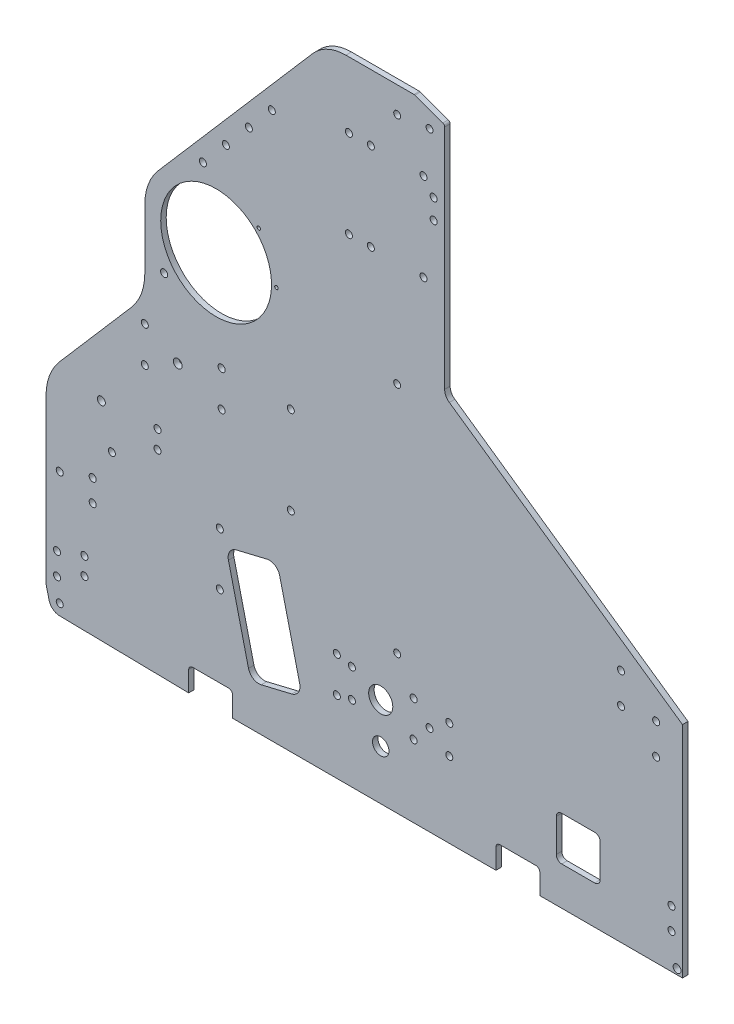
SolidWorks part; units mm, degrees
ref_plane "Front Plane" through (0, 0, 0) normal (0, 0, 1) x (1, 0, 0)
ref_plane "Top Plane" through (0, 0, 0) normal (0, 1, 0) x (1, 0, 0)
ref_plane "Right Plane" through (0, 0, 0) normal (1, 0, 0) x (0, 0, -1)
sketch "Sketch1" plane through (0, 0, 0) normal (0, 0, 1) x (1, 0, 0)
  line L0 (82.55, -20.32) -> (82.55, -6.35)
  line L2 (0, 0) -> (0, 157.48)
  line L4 (368.3, -20.32) -> (368.3, 106.68)
  line L5 (82.55, -6.35) -> (107.95, -6.35)
  line L6 (107.95, -6.35) -> (107.95, -20.32)
  line L7 (107.95, -20.32) -> (260.35, -20.32)
  line L8 (260.35, -20.32) -> (260.35, -6.35)
  line L9 (260.35, -6.35) -> (285.75, -6.35)
  line L10 (285.75, -6.35) -> (285.75, -20.32)
  line L11 (285.75, -20.32) -> (368.3, -20.32)
  line L12 (361.95, 12.7) -> (368.3, 12.7) construction
  line L13 (0, 0) -> (6.35, 0) construction
  line L14 (0.1896, -7.8901) -> (1.7771, -14.2401)
  line L15 (7.8295, -19.0491) -> (82.55, -20.32)
  line L16 (0, 0) -> (0, -6.35)
  line L17 (76.2, 141.605) -> (79.375, 141.605) construction
  line L18 (57.15, 131.2863) -> (101.6, 131.2862) construction
  line L19 (57.15, 131.2863) -> (57.15, 151.9238) construction
  line L20 (101.6, 131.2862) -> (101.6, 151.9237) construction
  line L21 (57.15, 151.9238) -> (101.6, 151.9237) construction
  line L22 (57.15, 131.2863) -> (101.6, 151.9237) construction
  line L23 (101.6, 131.2862) -> (57.15, 151.9238) construction
  line L25 (203.2, 59.805) -> (203.2, 194.805) construction
  line L26 (203.2, 194.805) -> (203.2, 329.805) construction
  line L27 (355.6, 332.105) -> (330.2, 332.105) construction
  line L28 (330.2, 332.105) -> (330.2, 217.805) construction
  line L29 (330.2, 217.805) -> (355.6, 217.805) construction
  line L30 (355.6, 217.805) -> (355.6, 332.105) construction
  line L31 (203.2, 344.805) -> (203.2, 194.805) construction
  line L32 (50.8, 332.105) -> (76.2, 332.105) construction
  line L33 (76.2, 332.105) -> (76.2, 217.805) construction
  line L34 (50.8, 217.805) -> (50.8, 332.105) construction
  line L35 (76.2, 217.805) -> (50.8, 217.805) construction
  line L36 (213.2, 344.805) -> (230.6638, 338.455)
  line L37 (203.2, 344.805) -> (161.925, 344.805)
  line L38 (203.2, 344.805) -> (213.2, 344.805)
  line L39 (348.5362, 344.805) -> (413.4623, 344.805)
  line L40 (348.5362, 344.805) -> (230.6638, 344.805) construction
  line L42 (161.925, 344.805) -> (0, 157.48)
  line L44 (230.6638, 338.455) -> (230.6638, 202.565)
  line L45 (230.6638, 202.565) -> (368.3, 106.68)
  line L46 (213.2, 344.805) -> (-141.0713, 344.805) construction
  circle A0 centre (6.35, 0) radius 2.032
  circle A1 centre (6.35, 12.7) radius 2.032
  circle A2 centre (361.95, 0) radius 2.032
  circle A3 centre (361.95, 12.7) radius 2.032
  arc A5 (1.7771, -14.2401) -> (7.8295, -19.0491) centre (7.9375, -12.7) ccw
  circle A6 centre (7.9375, -12.7) radius 2.032
  arc A7 (0, -6.35) -> (0.1896, -7.8901) centre (6.35, -6.35) ccw
  circle A8 centre (38.1, 78.105) radius 2.032
  circle A9 centre (76.2, 141.605) radius 2.54
  circle A10 centre (101.6, 131.2862) radius 2.032
  circle A11 centre (101.6, 151.9237) radius 2.032
  circle A12 centre (57.15, 151.9238) radius 2.032
  circle A13 centre (57.15, 131.2863) radius 2.032
  circle A15 centre (203.2, 59.805) radius 2
  circle A16 centre (203.2, 194.805) radius 2
  circle A17 centre (203.2, 329.805) radius 2
  circle A18 centre (63.5, 313.055) radius 2.032
  circle A20 centre (355.6, 332.105) radius 2.032
  circle A21 centre (330.2, 332.105) radius 2.032
  circle A22 centre (355.6, 217.805) radius 2.032
  circle A23 centre (330.2, 217.805) radius 2.032
  circle A24 centre (50.8, 332.105) radius 2.032
  circle A25 centre (76.2, 332.105) radius 2.032
  circle A26 centre (50.8, 217.805) radius 2.032
  circle A27 centre (76.2, 217.805) radius 2.032
  circle A28 centre (221.9319, 332.105) radius 2
  circle A29 centre (224.3138, 298.831) radius 2.032
  circle A30 centre (353.06, 100.7351) radius 2.032
  circle A31 centre (332.74, 115.9751) radius 2.032
  circle A32 centre (332.74, 98.1951) radius 2.032
  circle A33 centre (353.06, 82.9551) radius 2.032
  circle A34 centre (117.3562, 280.4276) radius 2.032
  circle A35 centre (104.0678, 265.0548) radius 2.032
  circle A36 centre (90.7795, 249.682) radius 2.032
  circle A38 centre (130.6445, 295.8004) radius 2.032
  circle A39 centre (68.326, 182.9237) radius 2.032
  circle A40 centre (224.3138, 287.401) radius 2.032
  point P82 (203.2, 344.805)
  point P83 (221.9319, 341.63)
  point P90 (368.3, 62.484)
  dimension "D6" = 4.064
  dimension "D10" = 6.35
  dimension "D11" = 4.064
  dimension "D17" = 38.1
  dimension "D27" = 4
  dimension "D31" = 4.064
  dimension "D32" = 41.275
  dimension "D36" = 4.064
  dimension "D47" = 39.624
  dimension "D48" = 4.064
  dimension "D25" = 5.08
  dimension "D26" = 4.064
  dimension "D52" = 4.064
  dimension "D65" = 4.064
  dimension "D2" = 127
  dimension "D3" = 13.97
  dimension "D4" = 25.4
  dimension "D5" = 152.4
  dimension "D7" = 12.7
  dimension "D8" = 6.35
  dimension "D9" = 20.32
  dimension "D12" = 12.7
  dimension "D13" = 1.5875
  dimension "D14" = 82.55
  dimension "D15" = 368.3
  dimension "D16" = 6.35
  dimension "D18" = 98.425
  dimension "D19" = 38.1
  dimension "D20" = 63.5
  dimension "D21" = 3.175
  dimension "D22" = 270
  dimension "D23" = 20.6375
  dimension "D24" = 44.45
  dimension "D28" = 135
  dimension "D29" = 12.7
  dimension "D30" = 15
  dimension "D33" = 63.5
  dimension "D34" = 27.4638
  dimension "D35" = 12.7
  dimension "D37" = 114.3
  dimension "D38" = 25.4
  dimension "D39" = 12.7
  dimension "D40" = 157.48
  dimension "D41" = 142.24
  dimension "D42" = 365.125
  dimension "D43" = 10
  dimension "D44" = 6.35
  dimension "D45" = 31.75
  dimension "D46" = 6.35
  dimension "D49" = 6.35
  dimension "D50" = 203.2
  dimension "D51" = 15.24
  dimension "D53" = 17.78
  dimension "D54" = 17.78
  dimension "D55" = 20.32
  dimension "D56" = 15.24
  dimension "D57" = 92.202
  dimension "D58" = 8.382
  dimension "D59" = 20.32
  dimension "D60" = 20.32
  dimension "D61" = 8.382
  dimension "D62" = 20.32
  dimension "D63" = 8.382
  dimension "D64" = 8.382
  dimension "D66" = 35.052
  dimension "D67" = 68.326
  dimension "D68" = 11.43
extrude "Boss-Extrude1" add sketch "Sketch1" along normal blind 3.175 contours L16 A7 L14 A5 L15 L2 A0 A1 A6 region at (171.3489, 119.5243, 0)
fillet "Fillet1" radius 2.286 4 edges at (285.75, -6.35, 1.5875) (107.95, -6.35, 1.5875) (260.35, -6.35, 1.5875) (82.55, -6.35, 1.5875)
fillet "Fillet2" radius 6.35 1 edges at (230.6638, 202.565, 1.5875)
sketch "Sketch2" plane through (0, 0, 0) normal (0, 0, -1) x (-1, 0, 0)
  circle A0 centre (-100.5528, 71.086) radius 2.032 construction
  circle A1 centre (-100.5528, 40.606) radius 2.032 construction
  circle A2 centre (-22.225, 18.2025) radius 2.032 construction
  circle A3 centre (-22.225, 8.0425) radius 2.032 construction
  circle A4 centre (-100.5528, 71.086) radius 2.032
  circle A5 centre (-100.5528, 40.606) radius 2.032
  circle A6 centre (-22.225, 18.2025) radius 2.032
  circle A7 centre (-22.225, 8.0425) radius 2.032
extrude "Cut-Extrude1" cut sketch "Sketch2" against normal through all
fillet "Fillet3" radius 1.5875 2 edges at (230.6638, 338.455, 1.5875) (213.2, 344.805, 1.5875)
sketch "Sketch3" plane through (0, 0, 3.175) normal (0, 0, 1) x (1, 0, 0)
  line L0 (132.9524, 63.2646) -> (132.7215, 64.2281) construction
  line L1 (128.3814, 66.8897) -> (110.6828, 62.6472) construction
  line L2 (114.5132, 58.4237) -> (126.8822, 61.3887) construction
  line L3 (108.0212, 58.3071) -> (108.2522, 57.3436) construction
  line L4 (131.2006, 57.703) -> (140.0164, 20.9265) construction
  line L5 (144.0993, 16.7636) -> (132.9524, 63.2646) construction
  line L6 (108.2522, 57.3436) -> (119.3991, 10.8426) construction
  line L7 (121.1509, 16.4042) -> (112.3351, 53.1807) construction
  line L8 (119.3991, 10.8426) -> (119.6301, 9.8791) construction
  line L9 (144.3303, 15.8001) -> (144.0993, 16.7636) construction
  line L10 (137.8383, 15.6835) -> (125.4694, 12.7185) construction
  line L11 (123.9701, 7.2175) -> (141.6687, 11.4601) construction
  line L12 (132.9524, 63.2646) -> (132.7215, 64.2281)
  line L13 (128.3814, 66.8897) -> (110.6828, 62.6472)
  line L14 (114.5132, 58.4237) -> (126.8822, 61.3887)
  line L15 (108.0212, 58.3071) -> (108.2522, 57.3436)
  line L16 (131.2006, 57.703) -> (140.0164, 20.9265)
  line L17 (144.0993, 16.7636) -> (132.9524, 63.2646)
  line L18 (108.2522, 57.3436) -> (119.3991, 10.8426)
  line L19 (121.1509, 16.4042) -> (112.3351, 53.1807)
  line L20 (119.3991, 10.8426) -> (119.6301, 9.8791)
  line L21 (144.3303, 15.8001) -> (144.0993, 16.7636)
  line L22 (137.8383, 15.6835) -> (125.4694, 12.7185)
  line L23 (123.9701, 7.2175) -> (141.6687, 11.4601)
  line L24 (127.7894, 69.3598) -> (110.0908, 65.1172)
  line L25 (105.5512, 57.715) -> (105.7822, 56.7515)
  line L26 (105.7822, 56.7515) -> (116.9291, 10.2505)
  line L27 (116.9291, 10.2505) -> (117.16, 9.287)
  line L28 (124.5622, 4.7475) -> (142.2608, 8.99)
  line L29 (146.8003, 16.3922) -> (146.5694, 17.3557)
  line L30 (146.5694, 17.3557) -> (135.4225, 63.8567)
  line L31 (135.4225, 63.8567) -> (135.1915, 64.8202)
  line L32 (14.605, -0.1369) -> (103.7278, 32.3011) construction
  line L33 (14.605, -0.1369) -> (103.7278, 32.3011)
  line L34 (0, -6.35) -> (0, 157.48) construction
  line L35 (-39.6666, 74.7152) -> (103.7278, 126.9065) construction
  line L36 (26.9875, 46.9531) -> (26.9875, 59.6531) construction
  line L37 (107.95, -20.32) -> (260.35, -20.32) construction
  line L38 (64.5259, 92.5258) -> (64.5259, 102.9405) construction
  arc A0 (132.7215, 64.2281) -> (128.6308, 66.9403) centre (129.2206, 63.3889) ccw construction
  arc A1 (110.6828, 62.6472) -> (110.4377, 62.5791) centre (111.522, 59.1463) ccw construction
  arc A2 (128.6308, 66.9403) -> (128.3814, 66.8897) centre (129.2206, 63.3889) ccw construction
  arc A3 (110.4377, 62.5791) -> (108.0212, 58.3071) centre (111.522, 59.1463) ccw construction
  arc A4 (119.6301, 9.8791) -> (123.7207, 7.1669) centre (123.1309, 10.7183) ccw construction
  arc A5 (141.9139, 11.5281) -> (144.3303, 15.8001) centre (140.8295, 14.9609) ccw construction
  arc A6 (141.6687, 11.4601) -> (141.9139, 11.5281) centre (140.8295, 14.9609) ccw construction
  arc A7 (123.7207, 7.1669) -> (123.9701, 7.2175) centre (123.1309, 10.7183) ccw construction
  arc A8 (132.7215, 64.2281) -> (128.6308, 66.9403) centre (129.2206, 63.3889) ccw
  arc A9 (110.6828, 62.6472) -> (110.4377, 62.5791) centre (111.522, 59.1463) ccw
  arc A10 (128.6308, 66.9403) -> (128.3814, 66.8897) centre (129.2206, 63.3889) ccw
  arc A11 (110.4377, 62.5791) -> (108.0212, 58.3071) centre (111.522, 59.1463) ccw
  arc A12 (119.6301, 9.8791) -> (123.7207, 7.1669) centre (123.1309, 10.7183) ccw
  arc A13 (141.9139, 11.5281) -> (144.3303, 15.8001) centre (140.8295, 14.9609) ccw
  arc A14 (141.6687, 11.4601) -> (141.9139, 11.5281) centre (140.8295, 14.9609) ccw
  arc A15 (123.7207, 7.1669) -> (123.9701, 7.2175) centre (123.1309, 10.7183) ccw
  arc A16 (110.0908, 65.1172) -> (109.6726, 65.0012) centre (111.522, 59.1463) ccw
  arc A17 (109.6726, 65.0012) -> (105.5512, 57.715) centre (111.522, 59.1463) ccw
  arc A18 (117.16, 9.287) -> (124.1369, 4.6613) centre (123.1309, 10.7183) ccw
  arc A19 (124.1369, 4.6613) -> (124.5622, 4.7475) centre (123.1309, 10.7183) ccw
  arc A20 (142.2608, 8.99) -> (142.6789, 9.1061) centre (140.8295, 14.9609) ccw
  arc A21 (142.6789, 9.1061) -> (146.8003, 16.3922) centre (140.8295, 14.9609) ccw
  arc A22 (135.1915, 64.8202) -> (128.2147, 69.446) centre (129.2206, 63.3889) ccw
  arc A23 (128.2147, 69.446) -> (127.7894, 69.3598) centre (129.2206, 63.3889) ccw
  circle A26 centre (133.35, 208.2281) radius 1.016 construction
  circle A33 centre (26.9875, 46.9531) radius 2.032
  circle A34 centre (26.9875, 59.6531) radius 2.032
  circle A35 centre (7.9375, 53.3031) radius 2.032
  circle A37 centre (32.0306, 100.8109) radius 31.75 construction
  circle A38 centre (32.0306, 100.8109) radius 2.286
  circle A39 centre (123.1207, 232.9238) radius 1.016 construction
  circle A40 centre (64.5259, 102.9405) radius 2.032
  circle A41 centre (64.5259, 92.5258) radius 2.032
  circle A42 centre (133.35, 208.2281) radius 1.016
  circle A43 centre (123.1207, 232.9238) radius 1.016
  ellipse E0 centre (124.5974, 48.8487) end of major axis (128.5376, 61.3578) minor radius 6 (131.2006, 57.703) -> (126.8822, 61.3887) ccw construction
  ellipse E1 centre (122.2349, 48.2824) end of major axis (113.0518, 57.6456) minor radius 6 (114.5132, 58.4237) -> (112.3351, 53.1807) ccw construction
  ellipse E2 centre (127.7541, 25.2585) end of major axis (131.6942, 37.7675) minor radius 6 (121.1509, 16.4042) -> (125.4694, 12.7185) ccw construction
  ellipse E3 centre (130.1166, 25.8248) end of major axis (139.2998, 16.4616) minor radius 6 (137.8383, 15.6835) -> (140.0164, 20.9265) ccw construction
  ellipse E4 centre (124.5974, 48.8487) end of major axis (120.6573, 36.3397) minor radius 6 (131.2006, 57.703) -> (126.8822, 61.3887) ccw
  ellipse E5 centre (122.2349, 48.2824) end of major axis (131.4181, 38.9192) minor radius 6 (114.5132, 58.4237) -> (112.3351, 53.1807) ccw
  ellipse E6 centre (127.7541, 25.2585) end of major axis (131.6942, 37.7675) minor radius 6 (121.1509, 16.4042) -> (125.4694, 12.7185) ccw
  ellipse E7 centre (130.1166, 25.8248) end of major axis (139.2998, 16.4616) minor radius 6 (137.8383, 15.6835) -> (140.0164, 20.9265) ccw
  point P93 (26.9875, 53.3031)
  point P115 (32.0306, 100.8109)
  dimension "D3" = 63.5
  dimension "D4" = 4.572
  dimension "D8" = 4.064
  dimension "D2" = 88.9
  dimension "D5" = 7.9375
  dimension "D6" = 19.05
  dimension "D7" = 73.6231
  dimension "D9" = 12.7
  dimension "D10" = 10.4147
  dimension "D11" = 37.5384
  dimension "D12" = 45.5727
  dimension "D1" = 2.54
extrude "Cut-Extrude2" cut sketch "Sketch3" against normal through all contours A22 A23 L24 A16 A17 L25 L26 L27 A18 A19 L28 A20 A21 L29 L30 L31 A15 A12 L20 L18 L15 A11 A9 L13 A10 A8 L12 L17 L21 A13 A14 L23 | A12 A15 L23 A14 A13 L21 L17 L12 A8 A10 L13 A9 A11 L15 L18 L20 E7 L22 E6 L19 E5 L14 E4 L16 | L22 E7 L16 E4 L14 E5 L19 E6 | A38 | A41 | A40 | A35 | A34 | A33 | A43 | A42 region at (137.844, 39.8506, 3.175) region at (126.1758, 37.0536, 3.175) region at (128.1544, 68.6507, 3.175) region at (32.0306, 100.8109, 3.175) region at (64.5259, 102.9405, 3.175) region at (64.5259, 92.5258, 3.175)
sketch "Sketch4" plane through (0, 0, 3.175) normal (0, 0, 1) x (1, 0, 0)
  line L0 (57.15, 151.9238) -> (101.6, 151.9237) construction
  line L1 (168.275, 21.4312) -> (212.725, 21.4312) construction
  line L2 (168.275, 21.4312) -> (168.275, 42.0687) construction
  line L3 (168.275, 42.0687) -> (212.725, 42.0687) construction
  line L4 (212.725, 21.4312) -> (212.725, 42.0687) construction
  line L5 (168.275, 21.4312) -> (212.725, 42.0687) construction
  line L6 (168.275, 42.0687) -> (212.725, 21.4312) construction
  line L7 (57.15, 131.2863) -> (57.15, 151.9238) construction
  line L8 (107.95, -20.32) -> (260.35, -20.32) construction
  line L9 (193.675, 31.75) -> (177.005, 31.75) construction
  line L10 (190.5, 31.75) -> (193.675, 31.75) construction
  line L11 (6.35, 12.7) -> (361.95, 12.7) construction
  line L12 (107.95, -6.35) -> (107.95, -20.32) construction
  line L13 (193.675, 31.75) -> (220.6625, 31.75) construction
  line L14 (177.005, 23.4569) -> (177.005, 40.0431) construction
  line L15 (213.2, 44.805) -> (193.2, 44.805) construction
  line L16 (213.2, 44.805) -> (213.2, 344.805) construction
  line L17 (213.2, 344.805) -> (193.2, 344.805) construction
  line L18 (193.2, 44.805) -> (193.2, 344.805) construction
  line L19 (213.2, 44.805) -> (193.2, 344.805) construction
  line L20 (213.2, 344.805) -> (193.2, 44.805) construction
  line L21 (226.9319, 332.105) -> (226.9319, 31.75) construction
  line L22 (237.33, 40.0431) -> (233.3612, 40.0431) construction
  line L23 (237.33, 23.4569) -> (233.3612, 23.4569) construction
  circle A0 centre (168.275, 42.0687) radius 2.032
  circle A1 centre (212.725, 42.0687) radius 2.032
  circle A2 centre (212.725, 21.4312) radius 2.032
  circle A3 centre (168.275, 21.4312) radius 2.032
  circle A4 centre (193.675, 31.75) radius 6.985
  circle A7 centre (220.6625, 31.75) radius 14.2875 construction
  circle A8 centre (193.675, 31.75) radius 12.7 construction
  circle A9 centre (177.005, 40.0431) radius 2.032
  circle A10 centre (177.005, 23.4569) radius 2.032
  circle A11 centre (237.33, 40.0431) radius 2.032 construction
  circle A12 centre (237.33, 23.4569) radius 2.032 construction
  circle A13 centre (193.675, 8.4667) radius 4.7625
  circle A14 centre (221.9319, 31.75) radius 2.032
  circle A15 centre (221.9319, 31.75) radius 5 construction
  circle A16 centre (221.9319, 332.105) radius 5 construction
  circle A17 centre (233.3612, 23.4569) radius 2.032
  circle A18 centre (233.3612, 40.0431) radius 2.032
  point P0 (190.5, 31.75)
  point P26 (203.2, 194.805)
  point P38 (177.005, 31.75)
  dimension "D1" = 4.064
  dimension "D4" = 13.97
  dimension "D7" = 9.525
  dimension "D10" = 25.4
  dimension "D11" = 28.575
  dimension "D16" = 10
  dimension "D17" = 4.064
  dimension "D18" = 10
  dimension "D2" = 52.07
  dimension "D3" = 3.175
  dimension "D5" = 82.55
  dimension "D6" = 26.9875
  dimension "D8" = 20
  dimension "D9" = 300
  dimension "D12" = 16.67
  dimension "D13" = 16.5862
  dimension "D14" = 60.325
  dimension "D15" = 23.2833
  dimension "D19" = 3.9688
extrude "Cut-Extrude3" cut sketch "Sketch4" against normal through all
sketch "Sketch5" plane through (0, 0, 0) normal (0, 0, -1) x (-1, 0, 0)
  line L0 (-57.15, 223.5947) -> (-57.15, 165.3337)
  line L1 (-161.925, 344.805) -> (-52.7201, 218.4699) construction
  line L2 (-57.15, 165.3337) -> (0, 99.219)
  line L3 (0, -6.35) -> (0, 157.48) construction
  line L5 (-50.4199, 215.8089) -> (0, 157.48) construction
  line L6 (-57.15, 223.5947) -> (0, 157.48)
  line L7 (0, 157.48) -> (0, 99.219)
  line L8 (-365.1708, -17.1908) -> (-368.3, -17.1908) construction
  line L9 (-365.1708, -17.1908) -> (-365.1708, -20.32) construction
  line L10 (-285.75, -20.32) -> (-368.3, -20.32) construction
  line L11 (-368.3, -20.32) -> (-368.3, 106.68) construction
  circle A0 centre (-98.425, 208.2281) radius 32.0675
  circle A2 centre (-365.1708, -17.1908) radius 2.286
  dimension "D3" = 64.135
  dimension "D7" = 4.572
  dimension "D1" = 38.1
  dimension "D2" = 57.15
  dimension "D4" = 41.275
  dimension "D5" = 41.275
  dimension "D6" = 3.1292
extrude "Cut-Extrude5" cut sketch "Sketch5" against normal through all contours A0 | L7 L6 L0 L2 | A2 region at (28.575, 161.4068, 0) region at (98.425, 208.2281, 0)
fillet "Fillet4" radius 31.75 3 edges at (0, 99.219, 1.5875) (57.15, 165.3337, 1.5875) (57.15, 223.5947, 1.5875)
sketch "Sketch6" plane through (0, 0, 3.175) normal (0, 0, 1) x (1, 0, 0)
  line L0 (285.75, -20.32) -> (368.3, -20.32) construction
  line L1 (298.45, 27.305) -> (317.5, 27.305)
  line L2 (295.275, 24.13) -> (295.275, 5.08)
  line L3 (298.45, 1.905) -> (317.5, 1.905)
  line L4 (320.675, 24.13) -> (320.675, 5.08)
  line L5 (295.275, 27.305) -> (320.675, 1.905) construction
  line L6 (295.275, 1.905) -> (320.675, 27.305) construction
  line L7 (368.3, -20.32) -> (368.3, 106.68) construction
  arc A0 (295.275, 5.08) -> (298.45, 1.905) centre (298.45, 5.08) ccw
  arc A1 (317.5, 1.905) -> (320.675, 5.08) centre (317.5, 5.08) ccw
  arc A2 (317.5, 27.305) -> (320.675, 24.13) centre (317.5, 24.13) cw
  arc A3 (298.45, 27.305) -> (295.275, 24.13) centre (298.45, 24.13) ccw
  point P0 (307.975, 14.605)
  dimension "D2" = 3.175
  dimension "D1" = 25.4
  dimension "D3" = 22.225
  dimension "D4" = 47.625
extrude "Cut-Extrude6" cut sketch "Sketch6" against normal through all
fillet "Fillet5" radius 25.4 1 edges at (161.925, 344.805, 1.5875)
sketch "Sketch8" plane through (0, 0, 0) normal (0, 0, -1) x (-1, 0, 0)
  circle A0 centre (-187.96, 306.705) radius 2.032 construction
  arc A1 (-176.3652, 304.9998) -> (-176.3652, 308.4102) centre (-175.26, 306.705) ccw construction
  arc A2 (-219.0586, 304.7695) -> (-219.0586, 308.6405) centre (-218.44, 306.705) ccw construction
  circle A3 centre (-205.74, 306.705) radius 2.032 construction
  arc A4 (-219.0586, 253.9695) -> (-219.0586, 257.8405) centre (-218.44, 255.905) ccw construction
  circle A5 centre (-205.74, 255.905) radius 2.032 construction
  circle A6 centre (-187.96, 255.905) radius 2.032 construction
  arc A7 (-176.3652, 254.1998) -> (-176.3652, 257.6102) centre (-175.26, 255.905) ccw construction
  circle A8 centre (-187.96, 306.705) radius 2.032
  arc A9 (-176.3652, 304.9998) -> (-176.3652, 308.4102) centre (-175.26, 306.705) ccw
  arc A10 (-219.0586, 304.7695) -> (-219.0586, 308.6405) centre (-218.44, 306.705) ccw
  circle A11 centre (-205.74, 306.705) radius 2.032
  arc A12 (-219.0586, 253.9695) -> (-219.0586, 257.8405) centre (-218.44, 255.905) ccw
  circle A13 centre (-205.74, 255.905) radius 2.032
  circle A14 centre (-187.96, 255.905) radius 2.032
  arc A15 (-176.3652, 254.1998) -> (-176.3652, 257.6102) centre (-175.26, 255.905) ccw
  circle A16 centre (-218.44, 306.705) radius 2.032
  circle A17 centre (-175.26, 306.705) radius 2.032
  circle A18 centre (-175.26, 255.905) radius 2.032
  circle A19 centre (-218.44, 255.905) radius 2.032
  circle A20 centre (-218.44, 306.705) radius 3.9687
  circle A21 centre (-205.74, 306.705) radius 3.9687
  circle A22 centre (-175.26, 306.705) radius 3.9687
  circle A23 centre (-218.44, 255.905) radius 3.9687
  circle A24 centre (-205.74, 255.905) radius 3.9687
  circle A25 centre (-187.96, 255.905) radius 3.9687
  circle A26 centre (-175.26, 255.905) radius 3.9687
  circle A27 centre (-187.96, 306.705) radius 3.9687
  dimension "D1" = 7.9375
extrude "Cut-Extrude7" cut sketch "Sketch8" against normal through all contours A10 A16 | A9 A17 | A15 A18 | A12 A19 | A8 | A14 region at (175.26, 306.705, 0) region at (218.44, 306.705, 0) region at (218.44, 255.905, 0) region at (175.26, 255.905, 0)
sketch "Sketch10" plane through (0, 0, 3.175) normal (0, 0, 1) x (1, 0, 0)
  circle A0 centre (141.6425, 151.3606) radius 2.032 construction
  circle A1 centre (141.6425, 100.5606) radius 2.032 construction
  circle A2 centre (141.6425, 151.3606) radius 2.032
  circle A3 centre (141.6425, 100.5606) radius 2.032
extrude "Cut-Extrude8" cut sketch "Sketch10" against normal through all
